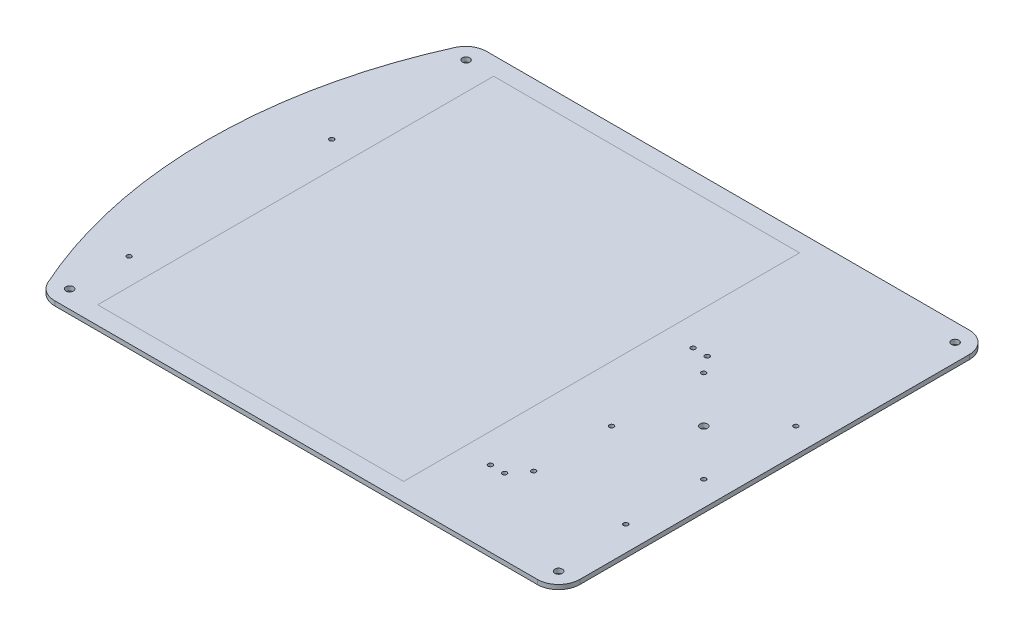
SolidWorks part; units mm, degrees
ref_plane "Front Plane" through (0, 0, 0) normal (0, 0, 1) x (1, 0, 0)
ref_plane "Top Plane" through (0, 0, 0) normal (0, 1, 0) x (1, 0, 0)
ref_plane "Right Plane" through (0, 0, 0) normal (1, 0, 0) x (0, 0, -1)
sketch "Sketch1" plane through (0, 0, 0) normal (0, -1, 0) x (1, 0, 0)
  line L0 (-315.0781, -152.4) -> (-62.2364, -152.4)
  line L1 (-315.0781, 152.4) -> (-62.2364, 152.4)
  line L2 (50, -50) -> (50, 50)
  line L3 (-62.2364, 152.4) -> (-39.8166, 97.5) construction
  line L4 (-72.05, 139.7) -> (-62.2364, 152.4) construction
  line L5 (0, 0) -> (-350, 0) construction
  line L6 (0, 0) -> (50, 0) construction
  line L7 (0, 0) -> (50, -50) construction
  line L8 (0, 0) -> (50, 50) construction
  line L9 (-72.05, -139.7) -> (-62.2364, -152.4) construction
  line L10 (-287.95, -139.7) -> (-72.05, -139.7) construction
  line L11 (-287.95, -139.7) -> (-287.95, 139.7) construction
  line L12 (-287.95, 139.7) -> (-72.05, 139.7) construction
  line L13 (-72.05, -139.7) -> (-72.05, 139.7) construction
  line L14 (-287.95, -139.7) -> (-72.05, 139.7) construction
  line L15 (-287.95, 139.7) -> (-72.05, -139.7) construction
  line L16 (-39.8166, 97.5) -> (40.7385, 97.5) construction
  line L17 (50, 50) -> (40.7385, 97.5) construction
  line L18 (0, 0) -> (-62.2364, -152.4) construction
  line L19 (-20.4188, -50) -> (50, -50) construction
  line L20 (0, 0) -> (-62.2364, 152.4) construction
  line L21 (-62.2364, -152.4) -> (-20.4188, -50) construction
  line L22 (50, -50) -> (50, -152.4)
  line L23 (50, -152.4) -> (-62.2364, -152.4)
  line L24 (50, 50) -> (50, 152.4)
  line L25 (50, 152.4) -> (-62.2364, 152.4)
  line L26 (25, -139.7) -> (-57.05, -139.7) construction
  line L27 (-57.05, -139.7) -> (-20.4188, -50) construction
  line L28 (-20.4188, -50) -> (25, -50) construction
  line L29 (25, -50) -> (25, -139.7) construction
  line L34 (-39.8166, 97.5) -> (25, 97.5) construction
  line L35 (-57.05, 139.7) -> (25, 139.7) construction
  line L36 (25, 139.7) -> (25, 97.5) construction
  line L37 (-39.8166, 97.5) -> (-57.05, 139.7) construction
  circle A0 centre (32.5, -32.5) radius 1.6
  circle A1 centre (32.5, 32.5) radius 1.6
  circle A2 centre (-32.5, -32.5) radius 1.6
  circle A3 centre (-32.5, 32.5) radius 1.6
  circle A4 centre (-32.5, 87.5) radius 1.6
  circle A5 centre (32.5, 87.5) radius 1.6
  circle A6 centre (24, 87.5) radius 1.7 construction
  circle A7 centre (-24, 87.5) radius 1.7 construction
  circle A8 centre (-24, 52.5) radius 1.7 construction
  circle A9 centre (24, 52.5) radius 1.7 construction
  circle A10 centre (24, 87.5) radius 1.7 construction
  circle A11 centre (-24, 87.5) radius 1.7 construction
  circle A12 centre (-24, 52.5) radius 1.7 construction
  circle A13 centre (24, 52.5) radius 1.7 construction
  circle A14 centre (7.5, -22) radius 1.6 construction
  circle A15 centre (-7.5, -22) radius 1.6 construction
  arc A16 (-315.0781, -152.4) -> (-315.0781, 152.4) centre (0, 0) cw
  circle A17 centre (0, 0) radius 2.65
  circle A18 centre (37.5, -139.9) radius 2.65
  circle A19 centre (-307.5781, -139.9) radius 2.65
  circle A20 centre (-307.5781, 139.9) radius 2.65
  circle A21 centre (37.5, 139.9) radius 2.65
  point P41 (-180, 0)
  dimension "D1" = 3.2
  dimension "D9" = 350
  dimension "D10" = 5.3
  dimension "D13" = 5.3
  dimension "D14" = 7.5
  dimension "D2" = 50
  dimension "D3" = 152.4
  dimension "D4" = 152.4
  dimension "D5" = 215.9
  dimension "D6" = 279.4
  dimension "D7" = 10
  dimension "D8" = 10
  dimension "D11" = 12.5
  dimension "D12" = 12.5
  dimension "D15" = 25
extrude "Boss-Extrude1" add sketch "Sketch1" along normal blind 3.175
fillet "Fillet1" radius 15 4 edges at (-315.0781, -1.5875, 152.4) (-315.0781, -1.5875, -152.4) (50, -1.5875, 152.4) (50, -1.5875, -152.4)
sketch "Sketch4" plane through (0, 0, 0) normal (0, 1, 0) x (1, 0, 0)
  line L0 (18.5, -106.5) -> (18.5, -91.5) construction
  line L1 (18.5, 36.5) -> (18.5, 51.5) construction
  line L2 (18.5, 44) -> (-281.5, 44) construction
  line L3 (-281.5, 45) -> (-281.5, 43) construction
  line L4 (18.5, -99) -> (-281.5, -99) construction
  line L5 (-281.5, -100) -> (-281.5, -98) construction
  line L6 (-281.5, 44) -> (-347.2233, 44) construction
  line L7 (-281.5, -99) -> (-335.7067, -99) construction
  circle A0 centre (-41.5, -99) radius 1.6
  circle A1 centre (-51.5, -99) radius 1.6
  circle A2 centre (-41.5, 44) radius 1.6
  circle A3 centre (-51.5, 44) radius 1.6
  arc A4 (-319.2064, 143.5522) -> (-319.2064, -143.5522) centre (0, 0) ccw construction
  arc A5 (-319.2064, 143.5522) -> (-319.2064, -143.5522) centre (0, 0) ccw construction
  circle A6 centre (-306.5, -99) radius 1.6
  circle A7 centre (-306.5, 44) radius 1.6
  point P33 (0, 0)
  dimension "D1" = 3.2
  dimension "D3" = 10
  dimension "D4" = 265
  dimension "D2" = 60
extrude "Cut-Extrude1" cut sketch "Sketch4" against normal up to surface (3.175 mm away) up to face at (-138.3322, -3.175, 0)
sketch "Sketch2" plane through (0, 0, 0) normal (0, 1, 0) x (1, 0, 0)
  line L1 (-287.95, 139.7) -> (-72.05, 139.7)
  line L2 (-287.95, 139.7) -> (-287.95, -139.7)
  line L3 (-287.95, -139.7) -> (-72.05, -139.7)
  line L4 (-72.05, 139.7) -> (-72.05, -139.7)
  line L5 (-287.95, 139.7) -> (-72.05, -139.7) construction
  line L6 (-287.95, -139.7) -> (-72.05, 139.7) construction
  point P0 (-180, 0)
  dimension "D1" = 279.4
  dimension "D2" = 215.9
wrap "Wrap1" sketch "Sketch2" wrap type scribe source sketch "Sketch2" face at (-306.5, 0, 100.6)
